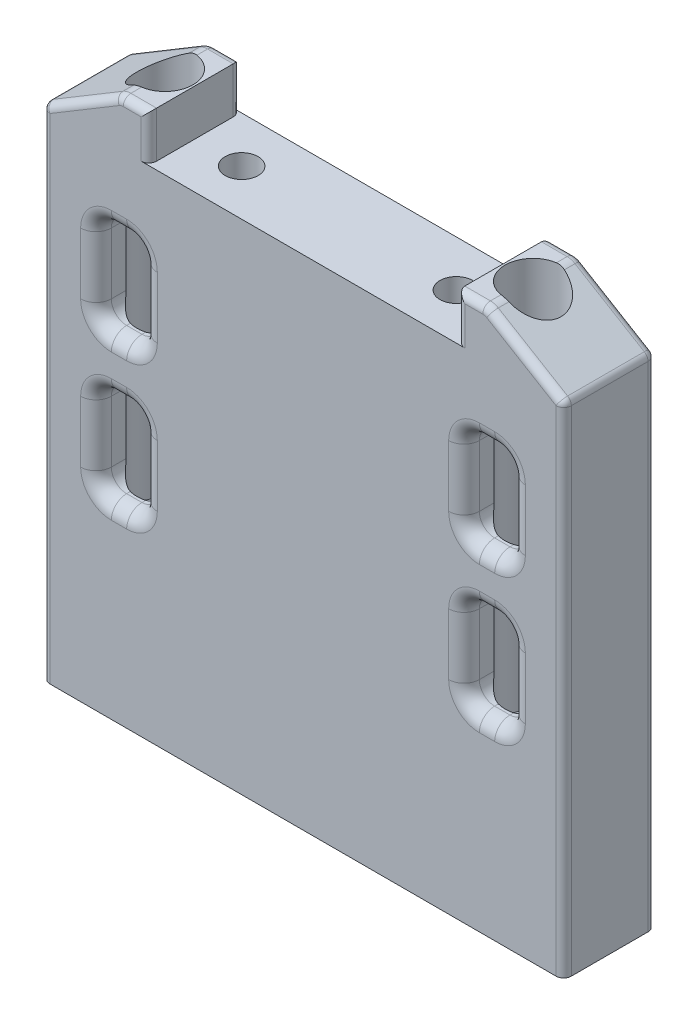
SolidWorks part; units mm, degrees
material "ABS"
ref_plane "前视基准面" through (0, 0, 0) normal (0, 0, 1) x (1, 0, 0)
ref_plane "上视基准面" through (0, 0, 0) normal (0, 1, 0) x (1, 0, 0)
ref_plane "右视基准面" through (0, 0, 0) normal (1, 0, 0) x (0, 0, -1)
other "Configuration Table"
sketch "草图1" plane through (0, 0, 0) normal (0, 0, 1) x (1, 0, 0)
  line L0 (0, 0) -> (68, 0)
  line L1 (68, 0) -> (68, 18)
  line L3 (54, 65) -> (14, 65)
  line L5 (0, 18) -> (0, 0)
  line L6 (14, 65) -> (14, 27)
  line L7 (14, 27) -> (0, 18)
  line L8 (54, 65) -> (54, 27)
  line L9 (54, 27) -> (68, 18)
  dimension "D1" = 14
  dimension "D2" = 18
  dimension "D3" = 65
  dimension "D5" = 68
  dimension "D6" = 38
  dimension "D8" = 14
extrude "凸台-拉伸1" add sketch "草图1" along normal mid plane 12
sketch "草图2" plane through (0, 65, 0) normal (0, 1, 0) x (1, 0, 0)
  line L0 (34, 6) -> (34, -6) construction
  line L1 (54, 6) -> (14, 6) construction
  line L2 (54, -6) -> (14, -6) construction
  line L3 (34, 0) -> (20, 0) construction
  line L4 (20, 0) -> (48, 0) construction
  circle A2 centre (48, 0) radius 2.1
  circle A3 centre (20, 0) radius 2.1
  dimension "D1" = 4.2
  dimension "D4" = 4.2
  dimension "D2" = 14
  dimension "D3" = 28
extrude "切除-拉伸1" cut sketch "草图2" against normal through all
sketch "草图3" plane through (0, 0, 0) normal (0, -1, 0) x (1, 0, 0)
  line L0 (34, 6) -> (34, -6) construction
  line L1 (0, 6) -> (68, 6) construction
  line L2 (0, -6) -> (68, -6) construction
  line L3 (0, 0) -> (10, 0) construction
  circle A0 centre (10, 0) radius 2.15
  circle A1 centre (58, 0) radius 2.15
  dimension "D1" = 4.3
  dimension "D2" = 10
extrude "切除-拉伸2" cut sketch "草图3" against normal through all
other "移动面1" flip direction yes face at (48, 0, 2.1) face at (20, 0, 2.1) offset 0.05 parameters "D1"=0.05
sketch "草图5" plane through (0, 65, 0) normal (0, 1, 0) x (1, 0, 0)
  circle A0 centre (10, 0) radius 3.65
  circle A1 centre (58, 0) radius 3.65
  dimension "D1" = 7.3
extrude "切除-拉伸4" cut sketch "草图5" against normal offset from surface (45 mm away) 20 up to face at (10, 0, -2.15)
sketch "草图6" plane through (0, 65, 0) normal (0, 1, 0) x (1, 0, 0)
  line L4 (14, 6) -> (0, 6)
  line L5 (0, 6) -> (0, -6)
  line L6 (0, -6) -> (14, -6)
  line L7 (14, -6) -> (14, 6)
  line L8 (14, 6) -> (0, 6)
  line L9 (0, 6) -> (0, -6)
  line L10 (0, -6) -> (14, -6)
  line L11 (14, -6) -> (14, 6)
  line L12 (68, 6) -> (54, 6)
  line L13 (54, 6) -> (54, -6)
  line L14 (54, -6) -> (68, -6)
  line L15 (68, -6) -> (68, 6)
  line L16 (68, 6) -> (54, 6)
  line L17 (54, 6) -> (54, -6)
  line L18 (54, -6) -> (68, -6)
  line L19 (68, -6) -> (68, 6)
  circle A0 centre (10, 0) radius 3.65 construction
  circle A1 centre (10, 0) radius 3.65
  circle A2 centre (58, 0) radius 3.65 construction
  circle A3 centre (58, 0) radius 3.65
  line M14 (54, -6) -> (54, 6)
  dimension "D1" = 0
  dimension "D2" = 0
extrude "凸台-拉伸2" add sketch "草图6" against normal up to surface (47 mm away) up to face at (13.65, 26.775, 0)
extrude "凸台-拉伸3" add sketch "草图6<2>" against normal up to surface (38 mm away) contours L18 L19 L16 A3 M14 region at (61.9954, 65, 0) up to face at (54.35, 26.775, 0)
sketch "草图6<2>" plane through (0, 65, 0) normal (0, 1, 0) x (1, 0, 0) same geometry as "草图6"
sketch "草图7" plane through (0, 65, 0) normal (0, 1, 0) x (1, 0, 0)
  line L0 (68, 6) -> (0, 6) construction
  line L1 (0, -6) -> (13.9, -6)
  line L2 (0, -6) -> (0, 6)
  line L3 (0, 6) -> (13.9, 6)
  line L4 (13.9, -6) -> (13.9, 6)
  line L5 (68, -6) -> (0, -6) construction
  line L6 (68, 6) -> (54.1, 6)
  line L7 (68, 6) -> (68, -6)
  line L8 (68, -6) -> (54.1, -6)
  line L9 (54.1, 6) -> (54.1, -6)
  circle A0 centre (58, 0) radius 3.65 construction
  circle A1 centre (10, 0) radius 3.65 construction
  circle A2 centre (58, 0) radius 3.65
  circle A3 centre (10, 0) radius 3.65
  dimension "D1" = 40.2
extrude "凸台-拉伸4" add sketch "草图7" along normal blind 6
sketch "草图8" plane through (0, 0, 6) normal (0, 0, 1) x (1, 0, 0)
  line L0 (0, 65) -> (0, 71)
  line L1 (0, 71) -> (0, 0) construction
  line L2 (0, 71) -> (10, 71)
  line L3 (0, 71) -> (13.9, 71) construction
  line L4 (10, 71) -> (0, 65)
  line L5 (34, 65) -> (34, 70.4364)
  line L6 (54.1, 65) -> (13.9, 65) construction
  line L7 (58, 71) -> (68, 65)
  line L8 (68, 71) -> (58, 71)
  line L9 (68, 65) -> (68, 71)
  line M4 (68, 0) -> (68, 71)
  line M5 (68, 71) -> (54.1, 71)
  line M9 (13.9, 71) -> (0, 71)
  line M10 (0, 71) -> (0, 0)
  dimension "D1" = 10
  dimension "D2" = 6
extrude "切除-拉伸5" cut sketch "草图8" against normal through all contours L4 M9 M10 | L7 M5 M4 region at (3.3333, 69, 6) region at (64.6667, 69, 6)
sketch "草图9" plane through (0, 0, 6) normal (0, 0, 1) x (1, 0, 0)
  line L0 (1, 40) -> (67, 40) construction
  line L1 (13, 43.5) -> (7, 43.5)
  line L2 (13, 43.5) -> (13, 55.5)
  line L3 (13, 55.5) -> (7, 55.5)
  line L4 (7, 43.5) -> (7, 55.5)
  line L5 (13, 43.5) -> (7, 55.5) construction
  line L6 (13, 55.5) -> (7, 43.5) construction
  line L7 (34, 65) -> (34, 0) construction
  line L8 (54.1, 65) -> (13.9, 65) construction
  line L9 (0, 0) -> (68, 0) construction
  line L10 (55, 55.5) -> (61, 55.5)
  line L11 (61, 43.5) -> (61, 55.5)
  line L12 (55, 43.5) -> (61, 43.5)
  line L13 (55, 43.5) -> (55, 55.5)
  line L14 (13, 24.5) -> (7, 36.5) construction
  line L15 (13, 36.5) -> (7, 24.5) construction
  line L16 (55, 36.5) -> (55, 24.5)
  line L17 (55, 36.5) -> (61, 36.5)
  line L18 (61, 36.5) -> (61, 24.5)
  line L19 (55, 24.5) -> (61, 24.5)
  line L20 (7, 36.5) -> (7, 24.5)
  line L21 (13, 24.5) -> (7, 24.5)
  line L22 (13, 36.5) -> (13, 24.5)
  line L23 (13, 36.5) -> (7, 36.5)
  point P0 (10, 49.5)
  point P25 (10, 30.5)
  dimension "D1" = 6
  dimension "D2" = 12
extrude "切除-拉伸6" cut sketch "草图9" against normal through all
fillet "圆角1" radius 2 32 edges at (13, 55.5, -4.0395) (13, 43.5, -4.0395) (7, 55.5, -4.0395) (61, 24.5, -4.0395) (55, 24.5, -4.0395) (55, 36.5, -4.0395) (61, 36.5, -4.0395) (7, 24.5, -4.0395) (7, 36.5, -4.0395) (13, 36.5, -4.0395) (13, 24.5, -4.0395) (61, 55.5, -4.0395) (61, 43.5, -4.0395) (55, 43.5, -4.0395) (55, 55.5, -4.0395) (7, 43.5, -4.0395) (13, 43.5, 4.0395) (13, 55.5, 4.0395) (7, 55.5, 4.0395) (55, 36.5, 4.0395) (55, 24.5, 4.0395) (61, 24.5, 4.0395) (61, 36.5, 4.0395) (13, 36.5, 4.0395) (7, 36.5, 4.0395) (7, 24.5, 4.0395) (13, 24.5, 4.0395) (55, 43.5, 4.0395) (61, 43.5, 4.0395) (61, 55.5, 4.0395) (55, 55.5, 4.0395) (7, 43.5, 4.0395)
fillet "圆角2" radius 2 64 edges at (12.4142, 35.9142, -6) (13, 30.5, -6) (12.4142, 25.0858, -6) (10, 24.5, -6) (7.5858, 25.0858, -6) (7, 30.5, -6) (7.5858, 35.9142, -6) (7.5858, 54.9142, -6) (10, 55.5, -6) (12.4142, 54.9142, -6) (13, 49.5, -6) (12.4142, 44.0858, -6) (10, 43.5, -6) (7.5858, 44.0858, -6) (55.5858, 35.9142, -6) (58, 36.5, -6) (60.4142, 35.9142, -6) (61, 30.5, -6) (60.4142, 25.0858, -6) (58, 24.5, -6) (55.5858, 25.0858, -6) (55.5858, 54.9142, -6) (58, 55.5, -6) (60.4142, 54.9142, -6) (61, 49.5, -6) (60.4142, 44.0858, -6) (58, 43.5, -6) (55.5858, 44.0858, -6) (58, 43.5, 6) (60.4142, 44.0858, 6) (61, 49.5, 6) (60.4142, 54.9142, 6) (58, 55.5, 6) (55.5858, 54.9142, 6) (55, 49.5, 6) (58, 24.5, 6) (60.4142, 25.0858, 6) (61, 30.5, 6) (60.4142, 35.9142, 6) (58, 36.5, 6) (55.5858, 35.9142, 6) (55, 30.5, 6) (10, 24.5, 6) (12.4142, 25.0858, 6) (13, 30.5, 6) (12.4142, 35.9142, 6) (10, 36.5, 6) (7.5858, 35.9142, 6) (7, 30.5, 6) (7.5858, 44.0858, 6) (7, 49.5, 6) (7.5858, 54.9142, 6) (10, 55.5, 6) (12.4142, 54.9142, 6) (13, 49.5, 6) (12.4142, 44.0858, 6) (10, 36.5, -6) (7, 49.5, -6) (55, 30.5, -6) (55, 49.5, -6) (55.5858, 44.0858, 6) (55.5858, 25.0858, 6) (7.5858, 25.0858, 6) (10, 43.5, 6)
fillet "圆角3" radius 2 4 edges at (58, 71, 4.825) (58, 71, -4.825) (10, 71, -4.825) (10, 71, 4.825)
fillet "圆角4" radius 1 22 edges at (4.7625, 67.8575, -6) (10.0201, 70.9274, -6) (4.7625, 67.8575, 6) (10.0201, 70.9274, 6) (55.773, 71, 6) (57.9799, 70.9274, 6) (55.773, 71, -6) (57.9799, 70.9274, -6) (12.227, 71, -6) (12.227, 71, 6) (63.2375, 67.8575, 6) (63.2375, 67.8575, -6) (68, 32.5, -6) (68, 32.5, 6) (68, 65, 0) (0, 32.5, -6) (0, 65, 0) (0, 32.5, 6) (13.9, 68, 6) (13.9, 68, -6) (54.1, 68, -6) (54.1, 68, 6)
